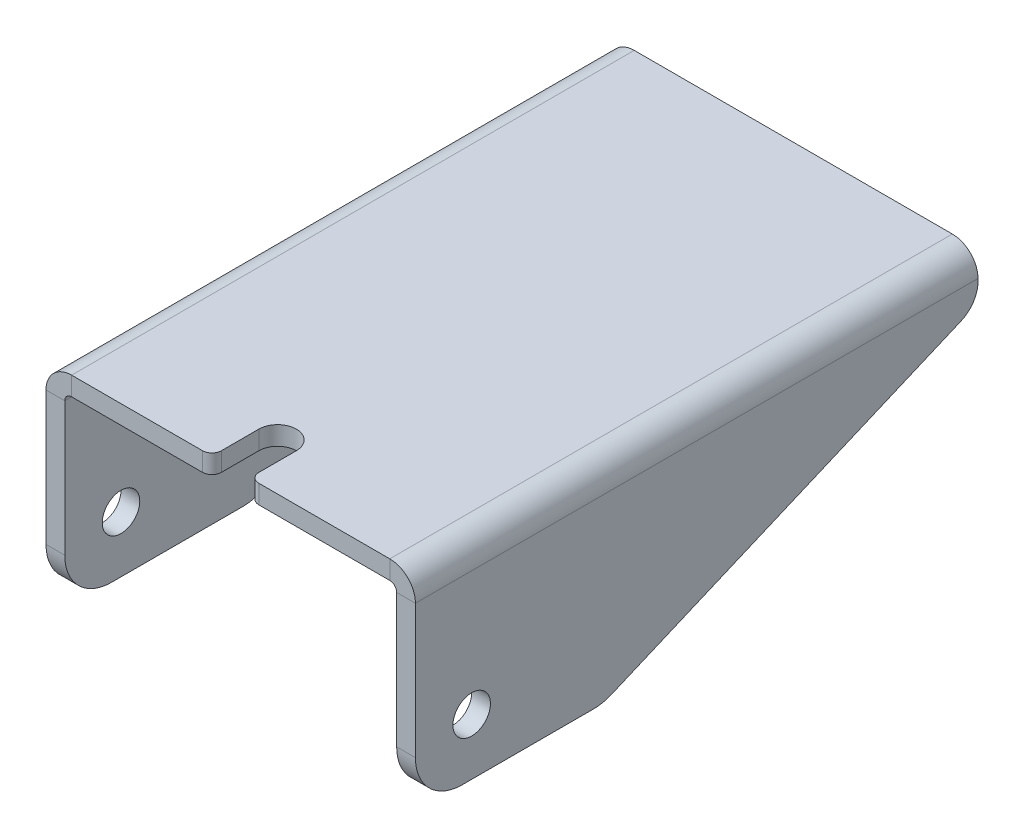
SolidWorks part; units mm, degrees
note: The reader was unsure of these and kept them because the rebuilt part matched: flange length of "Edge-Flange2".
ref_plane "Front Plane" through (0, 0, 0) normal (0, 0, 1) x (1, 0, 0)
ref_plane "Top Plane" through (0, 0, 0) normal (0, 1, 0) x (1, 0, 0)
ref_plane "Right Plane" through (0, 0, 0) normal (1, 0, 0) x (0, 0, -1)
sketch "Sketch1" plane through (0, 0, 0) normal (0, 1, 0) x (1, 0, 0)
  line L0 (0, 0) -> (-17.7, 0)
  line L1 (-17.7, 0) -> (-17.7, -60)
  line L2 (-17.7, -60) -> (0, -60)
  line L3 (0, -60) -> (0, 0)
  dimension "D1" = 17.7
  dimension "D2" = 60
base flange "Base-Flange2" sketch "Sketch1" thickness 2 reverse thickness direction no parameters "D1"=0.7366
edge flange "Edge-Flange2" sketch "Sketch15" flange angle 90 flange length 22 flange position material outside bend radius 0.7366 thickness 2 relief rectangular parameters "D6"=10
sketch "Sketch15" plane through (-17.7, -2, 0) normal (-1, 0, 0) x (0, 0, -1)
  line L0 (0, 0) -> (-60, 0) construction
  line L1 (0, 0) -> (-60, 0)
  line L2 (-60, 0) -> (-60, 20)
  line L3 (-60, 20) -> (0, 20)
  line L4 (0, 20) -> (0, 0)
bend "EdgeBend2" bend radius 0.7366 bend angle 90 parameters "D5"=1
sketch "Sketch20" plane through (-19.7, 0, 0) normal (-1, 0, 0) x (0, 0, 1)
  line L0 (0, -5) -> (40, -22)
  line L1 (0, -22) -> (0, -2) construction
  line L2 (0, -22) -> (60, -22) construction
  line L3 (40, -22) -> (0, -22)
  line L4 (0, -22) -> (0, -5)
  line L5 (0, -2.7366) -> (0, -22) construction
  line L6 (60, -22) -> (60, -2.7366) construction
  point P6 (0, -5.5532)
  dimension "D1" = 5
  dimension "D2" = 20
extrude "Cut-Extrude5" cut sketch "Sketch20" against normal up to surface (2 mm away) contours L0 L3 L4 normal cut yes up to face at (-17.7, -12.3683, 30)
fillet "Fillet4" radius 5 2 edges at (-18.7, -22, 40) (-18.7, -22, 60)
fillet "Fillet5" radius 3 1 edges at (-18.7, -5, 0)
sketch "Sketch22" plane through (-19.7, 0, 0) normal (-1, 0, 0) x (0, 0, 1)
  line L0 (60, -17) -> (60, -2.7366) construction
  line L1 (41.0184, -22) -> (55, -22) construction
  circle A0 centre (54, -16) radius 2
  dimension "D3" = 4
  dimension "D1" = 6
  dimension "D2" = 6
extrude "Cut-Extrude6" cut sketch "Sketch22" against normal up to surface (2 mm away) normal cut yes up to face at (-17.7, -12.2844, 32.1885)
mirror "Mirror1" about plane through (0, -2, 60) normal (1, 0, 0) of bodies 111
bend "MirrorBend1" bend radius 0.7366 bend angle 90 parameters "D5"=2
sketch "Sketch28" plane through (0, 0, 0) normal (0, 1, 0) x (1, 0, 0)
  line L0 (0, 0) -> (0, -60) construction
  line L1 (-16.9634, -60) -> (16.9634, -60) construction
  line L2 (2, -55) -> (2, -60)
  line L3 (-2, -55) -> (-2, -60)
  line L4 (-2, -60) -> (2, -60)
  arc A0 (2, -55) -> (-2, -55) centre (0, -55) ccw
  dimension "D2" = 2
  dimension "D1" = 5
extrude "Cut-Extrude7" cut sketch "Sketch28" against normal up to surface (2 mm away) normal cut yes up to face at (0, -2, 30)
fillet "Fillet6" radius 1 2 edges at (2, -1, 60) (-2, -1, 60)
sketch "Bend-Lines3" [suppressed] plane through (0, 0, 0) normal (0, 1, 0) x (1, 0, 0)
sketch "Bounding-Box3" [suppressed] plane through (0, 0, 0) normal (0, 1, 0) x (1, 0, 0)
sheet metal parameters "Sheet-Metal3" thickness 2 parameters "D1"=0.7366
flat pattern "Flat-Pattern3" [suppressed]
sketch "Bend-Lines4" plane through (0, 0, 0) normal (0, 1, 0) x (1, 0, 0)
sketch3d "Bounding-Box4" [suppressed]
  line L0 (17.7, 0, 0) -> (17.7, -60, 0) construction
  line L1 (0, 0, 0) -> (0, -60, 0) construction
  line L2 (17.7, 0, 0) -> (0, 0, 0) construction
  line L3 (17.7, -60, 0) -> (0, -60, 0) construction
sheet metal parameters "Sheet-Metal4" thickness 2 parameters "D1"=0.7366
flat pattern "Flat-Pattern3" [suppressed]
sketch "Bend-Lines4" plane through (0, 0, 0) normal (0, 1, 0) x (1, 0, 0)
  line L0 (-18.3273, 0) -> (-18.3273, -60) construction
  line L1 (-18.3273, 0) -> (-18.3273, -60) construction
sketch3d "Bounding-Box4" [suppressed]
  line L0 (-38.9546, 0, 0) -> (-38.9546, -60, 0) construction
  line L1 (0, 0, 0) -> (0, -60, 0) construction
  line L2 (-38.9546, 0, 0) -> (0, 0, 0) construction
  line L3 (-38.9546, -60, 0) -> (0, -60, 0) construction
bend of the flat pattern "Flatten-<EdgeBend2>1"
sketch "Sketch20-1" [suppressed] plane through (-16.9546, 0, 0) normal (0, 1, 0) x (0, 0, 1)
  line L0 (0, -5) -> (40, -22)
  line L3 (40, -22) -> (0, -22)
  line L4 (0, -22) -> (0, -5)
  line L6 (60, -22) -> (60, 16.9546) construction
  dimension "D1" = 21.9546
  dimension "D2" = 20
sheet metal parameters "Sheet-Metal7" thickness 2 parameters "D1"=0.7366
flat pattern "Flat-Pattern7"
sketch "Bend-Lines5" plane through (0, 0, 0) normal (0, 1, 0) x (1, 0, 0)
  line L0 (18.3273, -60) -> (18.3273, 0) construction
  line L1 (-18.3273, 0) -> (-18.3273, -60) construction
  line L2 (18.3273, -60) -> (18.3273, 0) construction
  line L3 (-18.3273, 0) -> (-18.3273, -60) construction
sketch3d "Bounding-Box5" [suppressed]
  line L0 (-38.9546, -60, 0) -> (38.9546, -60, 0) construction
  line L1 (-38.9546, 0, 0) -> (38.9546, 0, 0) construction
  line L2 (-38.9546, -60, 0) -> (-38.9546, 0, 0) construction
  line L3 (38.9546, -60, 0) -> (38.9546, 0, 0) construction
bend of the flat pattern "Flatten-<EdgeBend2>2"
bend of the flat pattern "Flatten-<MirrorBend1>1"
sheet metal parameters "Sheet-Metal10" thickness 2 parameters "D1"=0.7366
flat pattern "Flat-Pattern3" [suppressed]
sketch "Bend-Lines4" plane through (0, 0, 0) normal (0, 1, 0) x (1, 0, 0)
  line L0 (-18.3273, 0) -> (-18.3273, -60) construction
  line L1 (-18.3273, 0) -> (-18.3273, -60) construction
sketch3d "Bounding-Box4" [suppressed]
  line L0 (-38.9546, 0, 0) -> (-38.9546, -60, 0) construction
  line L1 (0, 0, 0) -> (0, -60, 0) construction
  line L2 (-38.9546, 0, 0) -> (0, 0, 0) construction
  line L3 (-38.9546, -60, 0) -> (0, -60, 0) construction
bend of the flat pattern "Flatten-<EdgeBend2>1"
sketch "Sketch20-1" [suppressed] plane through (-16.9546, 0, 0) normal (0, 1, 0) x (0, 0, 1)
  line L0 (0, -5) -> (40, -22)
  line L3 (40, -22) -> (0, -22)
  line L4 (0, -22) -> (0, -5)
  line L6 (60, -17) -> (60, 16.9546) construction
  dimension "D1" = 21.9546
  dimension "D2" = 20
sheet metal parameters "Sheet-Metal11" thickness 2 parameters "D1"=0.7366
flat pattern "Flat-Pattern3" [suppressed]
sketch "Bend-Lines4" plane through (0, 0, 0) normal (0, 1, 0) x (1, 0, 0)
  line L0 (-18.3273, 0) -> (-18.3273, -60) construction
  line L1 (-18.3273, 0) -> (-18.3273, -60) construction
sketch3d "Bounding-Box4" [suppressed]
  line L0 (-38.9546, 0, 0) -> (-38.9546, -60, 0) construction
  line L1 (0, 0, 0) -> (0, -60, 0) construction
  line L2 (-38.9546, 0, 0) -> (0, 0, 0) construction
  line L3 (-38.9546, -60, 0) -> (0, -60, 0) construction
bend of the flat pattern "Flatten-<EdgeBend2>1"
sketch "Sketch20-1" plane through (-16.9546, 0, 0) normal (0, 1, 0) x (0, 0, 1)
  line L0 (0, -5) -> (40, -22)
  line L3 (40, -22) -> (0, -22)
  line L4 (0, -22) -> (0, -5)
  line L6 (60, -17) -> (60, 16.9546) construction
  dimension "D1" = 21.9546
  dimension "D2" = 20
sketch "Sketch16-1" [suppressed] plane through (-16.9546, 0, 0) normal (0, 1, 0) x (0, 0, 1)
  line L0 (60, -7) -> (16.6077, -21.7345)
  line L3 (0, 16.9546) -> (0, -3.0153) construction
  line L5 (15, -22) -> (60, -22)
  line L6 (60, -22) -> (60, -7)
  arc A0 (16.6077, -21.7345) -> (15, -22) centre (15, -17) cw
  dimension "D1" = 5
  dimension "D2" = 15
  dimension "D4" = 15
sketch "Sketch18-1" [suppressed] plane through (-16.9546, 0, 0) normal (0, 1, 0) x (0, 0, 1)
  line L0 (60, 16.9546) -> (0, 16.9546) construction
  line L1 (0, 16.9546) -> (0, -3.0153) construction
  circle A0 centre (22, -16) radius 2
  dimension "D3" = 4
  dimension "D1" = 32.9546
  dimension "D2" = 22
sheet metal parameters "Sheet-Metal12" thickness 2 parameters "D1"=0.7366
flat pattern "Flat-Pattern7"
sketch "Bend-Lines5" plane through (0, 0, 0) normal (0, 1, 0) x (1, 0, 0)
  line L0 (18.3273, -60) -> (18.3273, 0) construction
  line L1 (-18.3273, 0) -> (-18.3273, -60) construction
  line L2 (18.3273, -60) -> (18.3273, 0) construction
  line L3 (-18.3273, 0) -> (-18.3273, -60) construction
sketch3d "Bounding-Box5" [suppressed]
  line L0 (-38.9546, -60, 0) -> (38.9546, -60, 0) construction
  line L1 (-38.9546, 0, 0) -> (38.9546, 0, 0) construction
  line L2 (-38.9546, -60, 0) -> (-38.9546, 0, 0) construction
  line L3 (38.9546, -60, 0) -> (38.9546, 0, 0) construction
bend of the flat pattern "Flatten-<EdgeBend2>2"
bend of the flat pattern "Flatten-<MirrorBend1>1"
